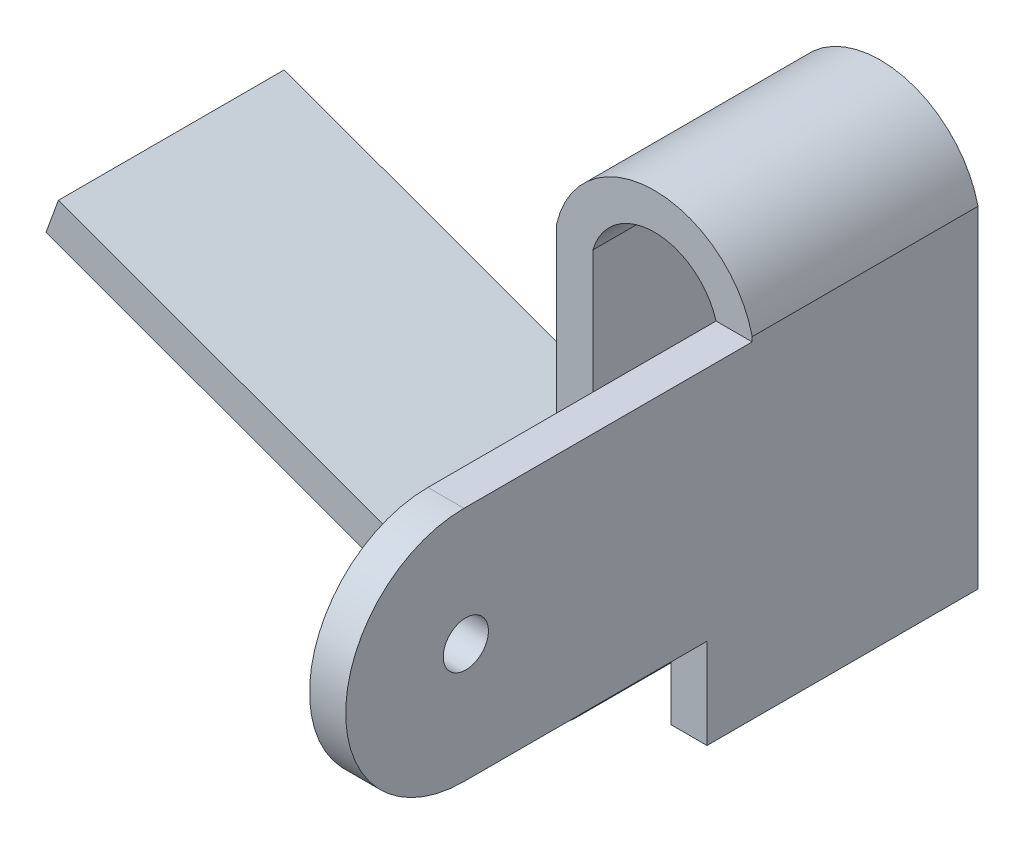
SolidWorks part; units mm, degrees
ref_plane "Front Plane" through (0, 0, 0) normal (0, 0, 1) x (1, 0, 0)
ref_plane "Top Plane" through (0, 0, 0) normal (0, 1, 0) x (1, 0, 0)
ref_plane "Right Plane" through (0, 0, 0) normal (1, 0, 0) x (0, 0, -1)
sketch "Sketch1" plane through (0, 0, 0) normal (0, 0, 1) x (1, 0, 0)
  line L0 (0, 0) -> (0, 3.67)
  line L1 (-2.1637, 3.67) -> (-2.1637, -0.5)
  line L2 (-2.5126, -0.7443) -> (-7.6809, 1.1368)
  line L3 (-0.4, 0) -> (-0.4, 3.6195)
  line L4 (-1.7637, 3.6195) -> (-1.7637, -0.5)
  line L5 (-2.6494, -1.1202) -> (-7.8177, 0.7609)
  line L6 (-7.8177, 0.7609) -> (-7.6809, 1.1368)
  line L7 (-0.4, 0) -> (0, 0)
  arc A0 (0, 3.67) -> (-2.1637, 3.67) centre (-1.0818, 3.4215) ccw
  arc A1 (-2.1637, -0.5) -> (-2.5126, -0.7443) centre (-2.4237, -0.5) cw
  arc A2 (-0.4, 3.6195) -> (-1.7637, 3.6195) centre (-1.0818, 3.4215) ccw
  arc A3 (-1.7637, -0.5) -> (-2.6494, -1.1202) centre (-2.4237, -0.5) cw
  dimension "D2" = 1.11
  dimension "D4" = 0.26
  dimension "D1" = 3.67
  dimension "D3" = 4.17
  dimension "D5" = 5.5
  dimension "D6" = 70
  dimension "D7" = 0.4
extrude "Boss-Extrude1" add sketch "Sketch1" along normal mid plane 2.5
sketch "Sketch2" plane through (0, 0, 1.25) normal (0, 0, 1) x (1, 0, 0)
  line L1 (0, 0) -> (-0.4, 0)
  line L2 (0, 0) -> (0, 3.6195)
  line L3 (0, 3.6195) -> (-0.4, 3.6195)
  line L4 (-0.4, 0) -> (-0.4, 3.6195)
extrude "Boss-Extrude2" add sketch "Sketch2" along normal blind 4.5
sketch "Sketch3" plane through (0, 0, 0) normal (1, 0, 0) x (0, 0, -1)
  line L1 (-5.75, 0) -> (-1.75, 0)
  line L2 (-5.75, 0) -> (-5.75, 1)
  line L3 (-5.75, 1) -> (-1.75, 1)
  line L4 (-1.75, 0) -> (-1.75, 1)
  dimension "D1" = 4
  dimension "D2" = 1
extrude "Cut-Extrude1" cut sketch "Sketch3" against normal blind 4.5
sketch "Sketch4" plane through (0, 0, 0) normal (1, 0, 0) x (0, 0, -1)
  line L0 (-5.75, 1) -> (-5.75, 3.6195) construction
  circle A0 centre (-4.42, 2.3098) radius 0.25
  point P4 (-5.75, 2.3098)
  dimension "D1" = 0.5
  dimension "D2" = 1.33
extrude "Cut-Extrude2" cut sketch "Sketch4" against normal blind 4.5
fillet "Fillet1" 2 edges at (-0.2, 3.6195, 5.75) (-0.2, 1, 5.75) type full round first side face at (-0.2, 3.6195, 3.5) second side face at (-0.2, 1, 3.75) middle face at (-0.2, 2.3098, 5.75)
